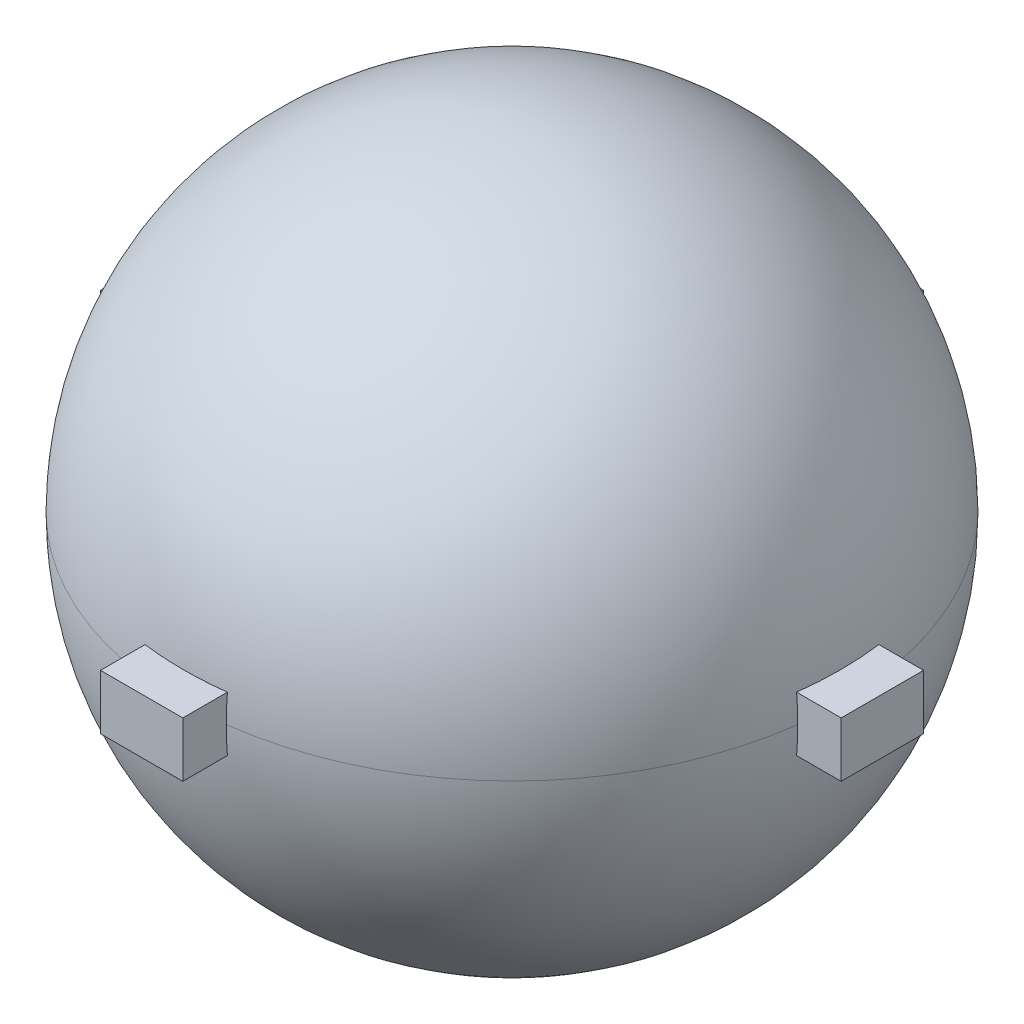
SolidWorks part; units mm, degrees
ref_plane "Front Plane" through (0, 0, 0) normal (0, 0, 1) x (1, 0, 0)
ref_plane "Top Plane" through (0, 0, 0) normal (0, 1, 0) x (1, 0, 0)
ref_plane "Right Plane" through (0, 0, 0) normal (1, 0, 0) x (0, 0, -1)
sketch "Sketch1" plane through (0, 0, 0) normal (0, 1, 0) x (1, 0, 0)
  circle A0 centre (0, 0) radius 304.8
  dimension "D1" = 609.6
extrude "Boss-Extrude1" add sketch "Sketch1" along normal blind 609.6
fillet "Fillet1" radius 304.8 2 edges at (0, 0, 304.8) (0, 609.6, 304.8)
shell "Shell2" thickness 3.175
ref_plane "Plane1" through (0, 304.8, 0) normal (0, 1, 0) x (1, 0, 0)
sketch "Sketch2" plane through (0, 304.8, 0) normal (0, 1, 0) x (1, 0, 0)
  line L0 (0, 0) -> (340.995, 0) construction
  line L1 (340.995, -63.5) -> (340.995, 63.5)
  point P5 (340.995, 0)
  dimension "D1" = 340.995
  dimension "D2" = 127
ref_plane "Plane2" through (342.5825, 0, 0) normal (1, 0, 0) x (0, 0, -1)
sketch "Sketch3" plane through (342.5825, 0, 0) normal (1, 0, 0) x (0, 0, -1)
  line L1 (-38.1, 279.4) -> (38.1, 279.4)
  line L2 (-38.1, 279.4) -> (-38.1, 330.2)
  line L3 (-38.1, 330.2) -> (38.1, 330.2)
  line L4 (38.1, 279.4) -> (38.1, 330.2)
  line L5 (-38.1, 279.4) -> (38.1, 330.2) construction
  line L6 (-38.1, 330.2) -> (38.1, 279.4) construction
  point P0 (0, 304.8)
  dimension "D1" = 50.8
  dimension "D2" = 76.2
extrude "Boss-Extrude2" add sketch "Sketch3" against normal up to surface (41.2417 mm away) up to face at (0, 304.8, -304.8)
pattern_circular "CirPattern1" count 4 over 360 about axis through (0, 304.8, 0) along (0, -1, 0) of "Boss-Extrude2"
